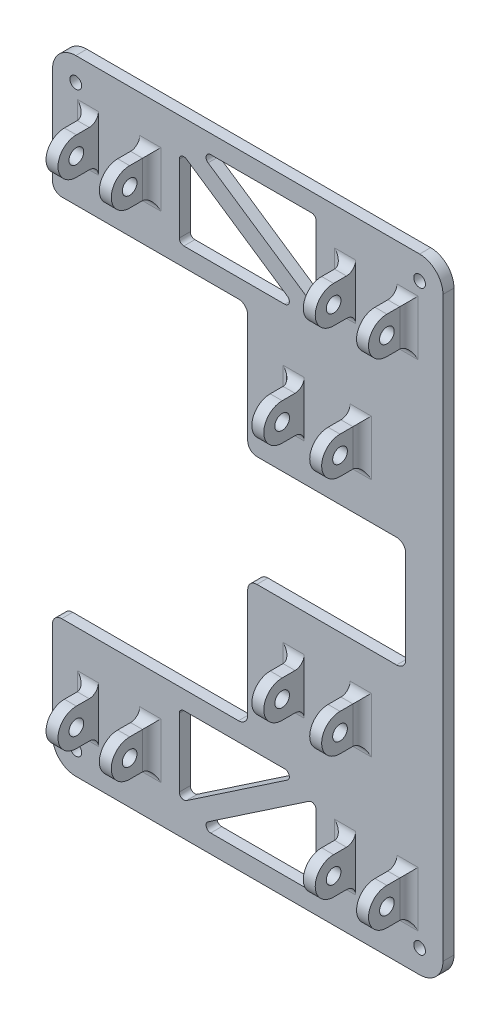
SolidWorks part; units mm, degrees
other "Markup3"
sketch "Sketch7" plane through (228.6, -342.9, 31.75) normal (0.076, -0.0024, 0.9971) x (0.9961, 0.0458, -0.0758)
other "Markup4"
sketch "Sketch8" plane through (228.6, -342.9, 31.75) normal (0.076, -0.0024, 0.9971) x (0.9961, 0.0458, -0.0758)
material "7075-T6 (SN)"
ref_plane "Front Plane" through (0, 0, 0) normal (0, 0, 1) x (1, 0, 0)
ref_plane "Top Plane" through (0, 0, 0) normal (0, 1, 0) x (1, 0, 0)
ref_plane "Right Plane" through (0, 0, 0) normal (1, 0, 0) x (0, 0, -1)
sketch "Sketch1" plane through (0, 0, 0) normal (0, 0, 1) x (1, 0, 0)
  line L1 (0, 0) -> (212.5, 0)
  line L2 (0, 0) -> (0, -339.725)
  line L3 (0, -339.725) -> (212.5, -339.725)
  line L4 (212.5, 0) -> (212.5, -339.725)
  dimension "D1" = 339.725
  dimension "D2" = 212.5
extrude "Boss-Extrude1" add sketch "Sketch1" along normal blind 6
sketch "Sketch2" plane through (0, 0, 6) normal (0, 0, 1) x (1, 0, 0)
  line L0 (0, 0) -> (0, -339.725) construction
  line L1 (25, -25.2425) -> (47.5, -25.2425) construction
  line L2 (25, -25.2425) -> (25, -45.2425)
  line L3 (25, -45.2425) -> (47.5, -45.2425) construction
  line L4 (47.5, -25.2425) -> (47.5, -45.2425)
  line L5 (165, -25.2425) -> (187.5, -25.2425) construction
  line L6 (165, -25.2425) -> (165, -45.2425)
  line L7 (165, -45.2425) -> (187.5, -45.2425) construction
  line L8 (187.5, -25.2425) -> (187.5, -45.2425)
  line L18 (137, -114.5325) -> (137, -225.1925) construction
  line L19 (0, -169.8625) -> (106.25, -169.8625) construction
  line L20 (54, -35.2425) -> (158.5, -35.2425) construction
  line L26 (165, -25.2425) -> (158.5, -25.2425)
  line L27 (165, -25.2425) -> (165, -45.2425)
  line L28 (165, -45.2425) -> (158.5, -45.2425)
  line L29 (158.5, -25.2425) -> (158.5, -45.2425)
  line L30 (187.5, -25.2425) -> (194, -25.2425)
  line L31 (187.5, -25.2425) -> (187.5, -45.2425)
  line L32 (187.5, -45.2425) -> (194, -45.2425)
  line L33 (194, -25.2425) -> (194, -45.2425)
  line L34 (47.5, -25.2425) -> (54, -25.2425)
  line L35 (47.5, -25.2425) -> (47.5, -45.2425)
  line L36 (47.5, -45.2425) -> (54, -45.2425)
  line L37 (54, -25.2425) -> (54, -45.2425)
  line L38 (25, -25.2425) -> (18.5, -25.2425)
  line L39 (25, -25.2425) -> (25, -45.2425)
  line L40 (25, -45.2425) -> (18.5, -45.2425)
  line L41 (18.5, -25.2425) -> (18.5, -45.2425)
  line L65 (212.5, -339.725) -> (212.5, 0) construction
  line L66 (137, -225.1925) -> (162, -225.1925) construction
  line L67 (158.5, -304.4825) -> (194, -304.4825) construction
  line L68 (149.5, -104.5325) -> (149.5, -235.1925) construction
  line L76 (18.5, -35.2425) -> (54, -35.2425) construction
  line L77 (18.5, -304.4825) -> (54, -304.4825) construction
  line L78 (36.25, -35.2425) -> (36.25, -304.4825) construction
  line L79 (137, -94.5325) -> (162, -94.5325) construction
  line L80 (54, -304.4825) -> (158.5, -304.4825) construction
  line L81 (106.25, -35.2425) -> (106.25, -304.4825) construction
  line L82 (106.25, -169.8625) -> (212.5, -169.8625) construction
  line L83 (130.5, -94.5325) -> (130.5, -114.5325)
  line L84 (137, -114.5325) -> (130.5, -114.5325)
  line L86 (137, -94.5325) -> (130.5, -94.5325)
  line L88 (137, -94.5325) -> (137, -114.5325)
  line L89 (162, -114.5325) -> (168.5, -114.5325)
  line L90 (162, -114.5325) -> (162, -94.5325)
  line L91 (168.5, -94.5325) -> (168.5, -114.5325)
  line L92 (162, -94.5325) -> (168.5, -94.5325)
  line L93 (130.5, -235.1925) -> (168.5, -235.1925) construction
  line L96 (137, -245.1925) -> (162, -245.1925) construction
  line L97 (162, -245.1925) -> (168.5, -245.1925)
  line L98 (168.5, -245.1925) -> (168.5, -225.1925)
  line L103 (130.5, -104.5325) -> (168.5, -104.5325) construction
  line L104 (137, -114.5325) -> (162, -114.5325) construction
  line L106 (158.5, -35.2425) -> (194, -35.2425) construction
  line L108 (176.25, -35.2425) -> (176.25, -304.4825) construction
  line L109 (165, -294.4825) -> (187.5, -294.4825) construction
  line L112 (165, -314.4825) -> (187.5, -314.4825) construction
  line L113 (25, -294.4825) -> (47.5, -294.4825) construction
  line L114 (25, -314.4825) -> (47.5, -314.4825) construction
  line L117 (162, -114.5325) -> (162, -225.1925) construction
  line L118 (18.5, -314.4825) -> (18.5, -294.4825)
  line L119 (25, -294.4825) -> (18.5, -294.4825)
  line L120 (25, -314.4825) -> (25, -294.4825)
  line L121 (25, -314.4825) -> (18.5, -314.4825)
  line L122 (54, -314.4825) -> (54, -294.4825)
  line L123 (47.5, -294.4825) -> (54, -294.4825)
  line L124 (47.5, -314.4825) -> (47.5, -294.4825)
  line L125 (47.5, -314.4825) -> (54, -314.4825)
  line L126 (194, -314.4825) -> (194, -294.4825)
  line L127 (187.5, -294.4825) -> (194, -294.4825)
  line L128 (187.5, -314.4825) -> (187.5, -294.4825)
  line L129 (187.5, -314.4825) -> (194, -314.4825)
  line L130 (158.5, -314.4825) -> (158.5, -294.4825)
  line L131 (165, -294.4825) -> (158.5, -294.4825)
  line L132 (165, -314.4825) -> (165, -294.4825)
  line L133 (165, -314.4825) -> (158.5, -314.4825)
  line L134 (187.5, -314.4825) -> (187.5, -294.4825)
  line L135 (165, -314.4825) -> (165, -294.4825)
  line L136 (47.5, -314.4825) -> (47.5, -294.4825)
  line L137 (25, -314.4825) -> (25, -294.4825)
  line L138 (162, -225.1925) -> (162, -245.1925)
  line L139 (162, -225.1925) -> (168.5, -225.1925)
  line L140 (137, -245.1925) -> (137, -225.1925)
  line L141 (137, -245.1925) -> (130.5, -245.1925)
  line L142 (137, -225.1925) -> (130.5, -225.1925)
  line L143 (130.5, -245.1925) -> (130.5, -225.1925)
  point P63 (194, -35.2425)
  point P101 (212.5, -169.8625)
  point P103 (158.5, -35.2425)
  dimension "D5" = 43.25
  dimension "D1" = 20
  dimension "D2" = 22.5
  dimension "D3" = 6.5
  dimension "D4" = 199.95
  dimension "D6" = 134.62
  dimension "D7" = 134.62
  dimension "D8" = 25
  dimension "D9" = 70
  dimension "D10" = 25
extrude "Boss-Extrude2" add sketch "Sketch2" along normal blind 24 contours L133 L132 L131 L130 | L128 L129 L126 L127 | L139 L138 L97 L98 | L143 L141 L140 L142 | L124 L125 L122 L123 | L121 L120 L119 L118 | L92 L90 L89 L91 | L88 L86 L83 L84 | L33 L30 L8 L32 | L37 L34 L4 L36 | L38 L41 L40 L2 | L26 L29 L28 L27 region at (21.75, -35.2425, 6) region at (50.75, -35.2425, 6) region at (190.75, -35.2425, 6) region at (133.75, -104.5325, 6) region at (165.25, -104.5325, 6) region at (165.25, -235.1925, 6) region at (21.75, -304.4825, 6) region at (50.75, -304.4825, 6) region at (190.75, -304.4825, 6) region at (161.75, -304.4825, 6) region at (133.75, -235.1925, 6)
sketch "Sketch3" plane through (18.5, 0, 0) normal (-1, 0, 0) x (0, 0, 1)
  line L0 (18, -104.5325) -> (6, -104.5325) construction
  line L1 (18, -304.4825) -> (6, -304.4825) construction
  line L2 (22, -235.1925) -> (37.7332, -235.1925) construction
  line L3 (22, -235.1925) -> (6, -235.1925) construction
  line L4 (18, -35.2425) -> (6, -35.2425) construction
  line L5 (6, -25.2425) -> (6, -45.2425) construction
  line L6 (6, -245.1925) -> (6, -225.1925) construction
  line L7 (6, 0) -> (6, -339.725) construction
  line L9 (18, -25.2425) -> (18, -12.9829)
  line L10 (18, -12.9829) -> (51.9495, -12.9829)
  line L11 (6, -245.1925) -> (6, -225.1925) construction
  line L12 (51.9495, -12.9829) -> (51.9495, -57.481)
  line L13 (51.9495, -57.481) -> (18, -57.481)
  line L14 (18, -57.481) -> (18, -45.2425)
  line L15 (52.4423, -132.3991) -> (18, -132.3991)
  line L16 (18, -94.5325) -> (18, -71.5915)
  line L17 (18, -71.5915) -> (52.4423, -71.5915)
  line L18 (18, -132.3991) -> (18, -114.5325)
  line L19 (52.4423, -71.5915) -> (52.4423, -132.3991)
  line L20 (52.5995, -270.3754) -> (18, -270.3754)
  line L21 (18, -225.1925) -> (18, -207.3064)
  line L22 (18, -207.3064) -> (52.5995, -207.3064)
  line L23 (18, -270.3754) -> (18, -245.1925)
  line L24 (52.5995, -207.3064) -> (52.5995, -270.3754)
  line L25 (52.621, -326.7211) -> (18, -326.7211)
  line L26 (18, -294.4825) -> (18, -282.2228)
  line L27 (18, -282.2228) -> (52.621, -282.2228)
  line L28 (18, -326.7211) -> (18, -314.4825)
  line L29 (52.621, -282.2228) -> (52.621, -326.7211)
  line L30 (6, -94.5325) -> (6, -114.5325) construction
  line L31 (30, -25.2425) -> (6, -25.2425) construction
  line L32 (30, -94.5325) -> (6, -94.5325) construction
  line L35 (6, -314.4825) -> (6, -294.4825) construction
  line L36 (6, -314.4825) -> (6, -294.4825) construction
  line L37 (18, -35.2425) -> (18, -104.5325) construction
  line L38 (18, -104.5325) -> (18, -235.1925) construction
  line L39 (18, -235.1925) -> (18, -304.4825) construction
  line L41 (30, -225.1925) -> (6, -225.1925) construction
  circle A0 centre (18, -35.2425) radius 4
  circle A1 centre (18, -235.1925) radius 4
  circle A2 centre (18, -35.2425) radius 5.5 construction
  circle A3 centre (18, -304.4825) radius 4
  circle A4 centre (18, -104.5325) radius 4
  arc A5 (18, -45.2425) -> (18, -25.2425) centre (18, -35.2425) ccw
  arc A6 (18, -114.5325) -> (18, -94.5325) centre (18, -104.5325) ccw
  arc A7 (18, -245.1925) -> (18, -225.1925) centre (18, -235.1925) ccw
  arc A8 (18, -314.4825) -> (18, -294.4825) centre (18, -304.4825) ccw
  point P62 (6, -304.4825)
  point P67 (6, -235.1925)
  dimension "D1" = 8
  dimension "D2" = 8
  dimension "D4" = 11
  dimension "D3" = 12
extrude "Cut-Extrude1" cut sketch "Sketch3" against normal through all both and the other way through all
fillet "Fillet2" radius 5 36 edges at (158.5, -304.4825, 6) (18.5, -304.4825, 6) (21.75, -45.2425, 6) (18.5, -35.2425, 6) (21.75, -25.2425, 6) (50.75, -25.2425, 6) (50.75, -45.2425, 6) (54, -35.2425, 6) (161.75, -25.2425, 6) (190.75, -25.2425, 6) (194, -35.2425, 6) (190.75, -45.2425, 6) (161.75, -45.2425, 6) (158.5, -35.2425, 6) (168.5, -104.5325, 6) (165.25, -114.5325, 6) (133.75, -114.5325, 6) (130.5, -104.5325, 6) (165.25, -94.5325, 6) (133.75, -94.5325, 6) (21.75, -294.4825, 6) (50.75, -294.4825, 6) (54, -304.4825, 6) (194, -304.4825, 6) (161.75, -294.4825, 6) (190.75, -294.4825, 6) (190.75, -314.4825, 6) (161.75, -314.4825, 6) (50.75, -314.4825, 6) (21.75, -314.4825, 6) (165.25, -225.1925, 6) (133.75, -225.1925, 6) (130.5, -235.1925, 6) (133.75, -245.1925, 6) (165.25, -245.1925, 6) (168.5, -235.1925, 6)
sketch "Sketch5" plane through (0, 0, 6) normal (0, 0, 1) x (1, 0, 0)
  line L0 (212.5, 0) -> (0, 0) construction
  line L1 (0, 0) -> (0, -339.725) construction
  line L2 (212.5, -339.725) -> (212.5, 0) construction
  line L5 (0, -169.8625) -> (212.5, -169.8625) construction
  line L6 (86.09, -10) -> (141, -10)
  line L7 (12.7, 0) -> (199.8, 0)
  line L8 (191.25, -104.5325) -> (191.25, -169.8625) construction
  line L9 (13.5, -50.2425) -> (59, -50.2425) construction
  line L10 (25, -50.2425) -> (13.5, -50.2425) construction
  line L11 (36.25, -50.2425) -> (36.25, -169.8625) construction
  line L12 (0, -274.2425) -> (0, -327.025)
  line L13 (12.7, -339.725) -> (199.8, -339.725)
  line L14 (212.5, -12.7) -> (212.5, -327.025)
  line L15 (173.5, -89.5325) -> (173.5, -119.5325) construction
  line L16 (106.25, 0) -> (106.25, -339.725) construction
  line L17 (173.5, -104.5325) -> (191.25, -104.5325) construction
  line L18 (5, -70.4825) -> (101.25, -70.4825)
  line L19 (0, -70.4825) -> (0, -269.2425)
  line L20 (5, -269.2425) -> (101.25, -269.2425)
  line L21 (106.25, -75.4825) -> (106.25, -134.7725)
  line L22 (47.5, -289.4825) -> (59, -289.4825) construction
  line L23 (173.5, -119.5325) -> (162, -119.5325) construction
  line L24 (111.25, -139.7725) -> (187.26, -139.7725)
  line L26 (0, -339.725) -> (212.5, -339.725) construction
  line L27 (111.25, -199.9525) -> (187.26, -199.9525)
  line L28 (192.26, -144.7725) -> (192.26, -194.9525)
  line L29 (162, -220.1925) -> (173.5, -220.1925) construction
  line L30 (69, -20.7429) -> (69, -57.8625)
  line L31 (71.5, -60.3625) -> (126.41, -60.3625)
  line L33 (59, -20.2425) -> (59, -50.2425) construction
  line L34 (379.0181, 152.7088) -> (433.9281, 152.7088)
  line L35 (72.9001, -18.6718) -> (127.8102, -55.7913)
  line L36 (143.5, -12.5) -> (143.5, -49.6196)
  line L37 (69, -10) -> (143.5, -60.3625) construction
  line L38 (84.6898, -14.5712) -> (139.5999, -51.6907)
  line L39 (361.9281, 141.9659) -> (361.9281, 104.8463)
  line L40 (364.4281, 102.3463) -> (419.3382, 102.3463)
  line L41 (365.8282, 144.037) -> (420.7383, 106.9175)
  line L42 (436.4281, 150.2088) -> (436.4281, 113.0892)
  line L43 (361.9281, 152.7088) -> (436.4281, 102.3463) construction
  line L44 (377.618, 148.1377) -> (432.528, 111.0181)
  line L45 (71.5, -279.3625) -> (126.41, -279.3625)
  line L46 (69, -318.9821) -> (69, -281.8625)
  line L47 (72.9001, -321.0532) -> (127.8102, -283.9337)
  line L48 (84.6898, -325.1538) -> (139.5999, -288.0343)
  line L49 (86.09, -329.725) -> (141, -329.725)
  line L50 (143.5, -327.225) -> (143.5, -290.1054)
  line L51 (106.25, -204.9525) -> (106.25, -264.2425)
  line L52 (0, -12.7) -> (0, -65.4825)
  line L54 (0, 0) -> (212.5, 0)
  line L55 (0, 0) -> (0, -339.725)
  line L56 (0, -339.725) -> (212.5, -339.725)
  line L57 (212.5, 0) -> (212.5, -339.725)
  circle A0 centre (12.7, -12.7) radius 3.175
  circle A1 centre (199.8, -12.7) radius 3.175
  circle A11 centre (12.7, -327.025) radius 3.175
  circle A12 centre (199.8, -327.025) radius 3.175
  arc A16 (12.7, 0) -> (0, -12.7) centre (12.7, -12.7) ccw
  arc A17 (0, -327.025) -> (12.7, -339.725) centre (12.7, -327.025) ccw
  arc A18 (199.8, -339.725) -> (212.5, -327.025) centre (199.8, -327.025) ccw
  arc A19 (212.5, -12.7) -> (199.8, 0) centre (199.8, -12.7) ccw
  arc A20 (72.9001, -18.6718) -> (69, -20.7429) centre (71.5, -20.7429) ccw
  arc A21 (126.41, -60.3625) -> (127.8102, -55.7913) centre (126.41, -57.8625) ccw
  arc A22 (69, -57.8625) -> (71.5, -60.3625) centre (71.5, -57.8625) ccw
  arc A23 (84.6898, -14.5712) -> (86.09, -10) centre (86.09, -12.5) cw
  arc A24 (139.5999, -51.6907) -> (143.5, -49.6196) centre (141, -49.6196) ccw
  arc A25 (141, -10) -> (143.5, -12.5) centre (141, -12.5) cw
  arc A26 (365.8282, 144.037) -> (361.9281, 141.9659) centre (364.4281, 141.9659) ccw
  arc A27 (419.3382, 102.3463) -> (420.7383, 106.9175) centre (419.3382, 104.8463) ccw
  arc A28 (361.9281, 104.8463) -> (364.4281, 102.3463) centre (364.4281, 104.8463) ccw
  arc A29 (377.618, 148.1377) -> (379.0181, 152.7088) centre (379.0181, 150.2088) cw
  arc A30 (432.528, 111.0181) -> (436.4281, 113.0892) centre (433.9281, 113.0892) ccw
  arc A31 (433.9281, 152.7088) -> (436.4281, 150.2088) centre (433.9281, 150.2088) cw
  arc A32 (69, -281.8625) -> (71.5, -279.3625) centre (71.5, -281.8625) cw
  arc A33 (72.9001, -321.0532) -> (69, -318.9821) centre (71.5, -318.9821) cw
  arc A34 (126.41, -279.3625) -> (127.8102, -283.9337) centre (126.41, -281.8625) cw
  arc A35 (84.6898, -325.1538) -> (86.09, -329.725) centre (86.09, -327.225) ccw
  arc A36 (141, -329.725) -> (143.5, -327.225) centre (141, -327.225) ccw
  arc A37 (139.5999, -288.0343) -> (143.5, -290.1054) centre (141, -290.1054) cw
  arc A38 (5, -269.2425) -> (0, -274.2425) centre (5, -274.2425) ccw
  arc A39 (101.25, -269.2425) -> (106.25, -264.2425) centre (101.25, -264.2425) ccw
  arc A40 (106.25, -204.9525) -> (111.25, -199.9525) centre (111.25, -204.9525) cw
  arc A41 (187.26, -199.9525) -> (192.26, -194.9525) centre (187.26, -194.9525) ccw
  arc A42 (187.26, -139.7725) -> (192.26, -144.7725) centre (187.26, -144.7725) cw
  arc A43 (111.25, -139.7725) -> (106.25, -134.7725) centre (111.25, -134.7725) cw
  arc A44 (101.25, -70.4825) -> (106.25, -75.4825) centre (101.25, -75.4825) cw
  arc A45 (5, -70.4825) -> (0, -65.4825) centre (5, -65.4825) cw
  point P10 (0, 0)
  point P20 (212.5, -339.725)
  point P130 (106.25, -269.2425)
  dimension "D1" = 93.55
  dimension "D3" = 12.7
  dimension "D5" = 85
  dimension "D6" = 20.24
  dimension "D7" = 20.24
  dimension "D8" = 6.35
  dimension "D9" = 20.24
  dimension "D10" = 20.24
  dimension "D11" = 10
  dimension "D12" = 2.5
  dimension "D13" = 10.12
  dimension "D14" = 2.5
  dimension "D15" = 5
  dimension "D17" = 2.5
  dimension "D18" = 2.5
  dimension "D19" = 5
  dimension "D21" = 2.5
  dimension "D22" = 2.5
  dimension "D23" = 2.5
  dimension "D24" = 2.5
  dimension "D25" = 5
  dimension "D26" = 5
  dimension "D2" = 157.1625
  dimension "D4" = 20.24
  dimension "D16" = 5
  dimension "D20" = 5
extrude "Cut-Extrude2" cut sketch "Sketch5" against normal through all contours L30 A22 L31 A21 L35 A20 | A25 L6 A23 L38 A24 L36 | L18 A45 L55 L19 A38 L20 A39 L51 A40 L27 A41 L28 A42 L24 A43 L21 A44 | A37 L48 A35 L49 A36 L50 | A34 L45 A32 L46 A33 L47 | A1 | A0 | A11 | A18 L56 L57 | A17 L55 L56 | A16 L54 L55 | A19 L57 L54 | A12 region at (121.8937, -24.8097, 6) region at (2.8368, -2.8368, 6) region at (209.6632, -2.8368, 6) region at (71.9717, -169.8625, 6) region at (209.6632, -336.8882, 6) region at (2.8368, -336.8882, 6) region at (90.6063, -45.5528, 6) region at (90.6063, -294.1722, 6) region at (121.8937, -314.9153, 6) region at (12.7, -12.7, 6) region at (199.8, -12.7, 6) region at (12.7, -327.025, 6)
sketch3d "3DSketch1"
  line L0 (18.5, -35.2425, 18) -> (194, -35.2425, 18) construction
  line L1 (25, -35.2425, 18) -> (18.5, -35.2425, 18) construction
  line L2 (194, -35.2425, 18) -> (187.5, -35.2425, 18) construction
  line L3 (194, -35.2425, 18) -> (187.5, -35.2425, 18) construction
  line L5 (194, -304.4825, 18) -> (187.5, -304.4825, 18) construction
  line L6 (194, -304.4825, 18) -> (18.5, -304.4825, 18) construction
  line L7 (25, -304.4825, 18) -> (18.5, -304.4825, 18) construction
  circle A0 centre (194, -35.2425, 18) radius 4 construction
  point P17 (198, -35.2425, 18)
  point P18 (194, -35.2425, 18)
